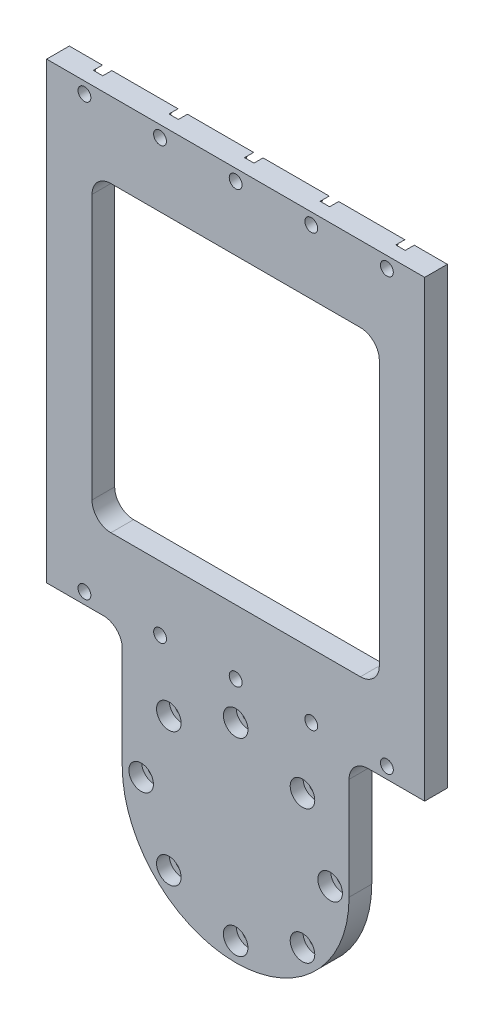
SolidWorks part; units mm, degrees
material "6061-T6 (SS)"
ref_plane "Front Plane" through (0, 0, 0) normal (0, 0, 1) x (1, 0, 0)
ref_plane "Top Plane" through (0, 0, 0) normal (0, 1, 0) x (1, 0, 0)
ref_plane "Right Plane" through (0, 0, 0) normal (1, 0, 0) x (0, 0, -1)
sketch "Sketch1" plane through (0, 0, 0) normal (0, 0, 1) x (1, 0, 0)
  line L0 (-30, 0) -> (-30, 152)
  line L1 (-30, 152) -> (30, 152)
  line L2 (30, 152) -> (30, 0)
  arc A0 (-30, 0) -> (30, 0) centre (0, 0) ccw
  dimension "D1" = 60
  dimension "D2" = 152
extrude "Boss-Extrude1" add sketch "Sketch1" along normal blind 6
sketch "Sketch7" plane through (0, 0, 6) normal (0, 0, 1) x (1, 0, 0)
  line L1 (30, 152) -> (50, 152)
  line L2 (30, 152) -> (30, 32)
  line L3 (30, 32) -> (50, 32)
  line L4 (50, 152) -> (50, 32)
  line L5 (-30, 152) -> (-50, 152)
  line L6 (-30, 152) -> (-30, 32)
  line L7 (-30, 32) -> (-50, 32)
  line L8 (-50, 152) -> (-50, 32)
  dimension "D1" = 100
  dimension "D2" = 32
extrude "Boss-Extrude2" add sketch "Sketch7" against normal up to surface (6 mm away) up to face at (0, 68.5, 0)
sketch "Sketch2" plane through (0, 0, 6) normal (0, 0, 1) x (1, 0, 0)
  circle A0 centre (0, 0) radius 25
  point P6 (0, 25)
  point P12 (17.6777, 17.6777)
  point P13 (25, 0)
  point P14 (17.6777, -17.6777)
  point P15 (0, -25)
  point P16 (-17.6777, -17.6777)
  point P17 (-25, 0)
  point P18 (-17.6777, 17.6777)
  dimension "D1" = 50
  dimension "D2" = 8
hole_wizard "CBORE for M3 Hex Socket Head Cap Screw1" positions "Sketch2" profile "Sketch3" counterbore size "M3" standard "DIN" end condition through all
sketch "Sketch3" plane through (-17.6777, 17.6777, 6) normal (1, 0, 0) x (0, -1, 0)
  line L0 (0, 0) -> (0, 6)
  line L1 (0, 6) -> (1.7, 6)
  line L3 (1.7, 6) -> (1.7, 3.4)
  line L4 (1.7, 3.4) -> (3.25, 3.4)
  line L5 (3.25, 3.4) -> (3.25, 0)
  line L7 (3.25, 0) -> (0, 0)
  line L11 (0, -6.35) -> (0, 107.95) construction
  dimension "Thru Hole Dia." = 3.4
  dimension "Thru Hole Depth" = 6
  dimension "C'Bore Dia." = 6.5
  dimension "C'Bore Depth" = 3.4
sketch "Sketch4" plane through (0, 0, 0) normal (0, 0, -1) x (-1, 0, 0)
  line L0 (-30, 35) -> (30, 35) construction
  line L1 (30, 32) -> (30, 0) construction
  line L2 (-30, 0) -> (-30, 32) construction
  line L3 (-50, 152) -> (50, 152) construction
  line L4 (0, 152) -> (0, 149) construction
  point P7 (0, 35)
  point P23 (20, 35)
  point P24 (40, 35)
  point P25 (0, 35)
  point P26 (20, 35)
  point P27 (-20, 35)
  point P28 (0, 35)
  point P29 (-20, 35)
  point P30 (-40, 35)
  point P46 (0, 149)
  point P59 (20, 149)
  point P60 (40, 149)
  point P61 (0, 149)
  point P62 (20, 149)
  point P63 (-20, 149)
  point P64 (0, 149)
  point P65 (-20, 149)
  point P66 (-40, 149)
  dimension "D1" = 35
  dimension "D5" = 3
  dimension "D4" = 3
  dimension "D6" = 3
  dimension "D3" = 3
  dimension "D2" = 3
hole_wizard "CBORE for M3 Hex Socket Thin Head Cap Screw1" positions "Sketch4" profile "Sketch6" counterbore size "M3" standard "DIN"
sketch "Sketch6" plane through (40, 149, 0) normal (1, 0, 0) x (0, 1, 0)
  line L0 (0, 0) -> (0, 11.0215)
  line L1 (0, 11.0215) -> (1.7, 10)
  line L2 (1.7, 10) -> (1.7, 2.4)
  line L3 (1.7, 2.4) -> (3.25, 2.4)
  line L4 (3.25, 2.4) -> (3.25, 0)
  line L5 (3.25, 0) -> (0, 0)
  line L10 (0, 11.0215) -> (-1.7, 10) construction
  line L11 (0, -6.35) -> (0, 107.95) construction
  dimension "Hole Dia." = 3.4
  dimension "Hole Depth" = 10
  dimension "C'Bore Dia." = 6.5
  dimension "C'Bore Depth" = 2.4
  dimension "Drill Angle" = 118
fillet "Fillet1" radius 5 2 edges at (30, 32, 3) (-30, 32, 3)
sketch "Sketch8" plane through (0, 0, 0) normal (0, 0, -1) x (-1, 0, 0)
  line L0 (50, 32) -> (50, 152) construction
  line L1 (-38, 132) -> (38, 132)
  line L2 (-38, 132) -> (-38, 52)
  line L3 (-38, 52) -> (38, 52)
  line L4 (38, 132) -> (38, 52)
  line L5 (-50, 152) -> (-50, 32) construction
  line L6 (-38.75, 152) -> (-21.25, 152) construction
  line L7 (-50, 32) -> (-41.25, 32) construction
  dimension "D1" = 12
  dimension "D2" = 12
  dimension "D3" = 20
  dimension "D4" = 20
extrude "Cut-Extrude1" cut sketch "Sketch8" against normal up to next and the other way through all
fillet "Fillet2" radius 5 4 edges at (-38, 52, 3) (38, 52, 3) (38, 132, 3) (-38, 132, 3)
